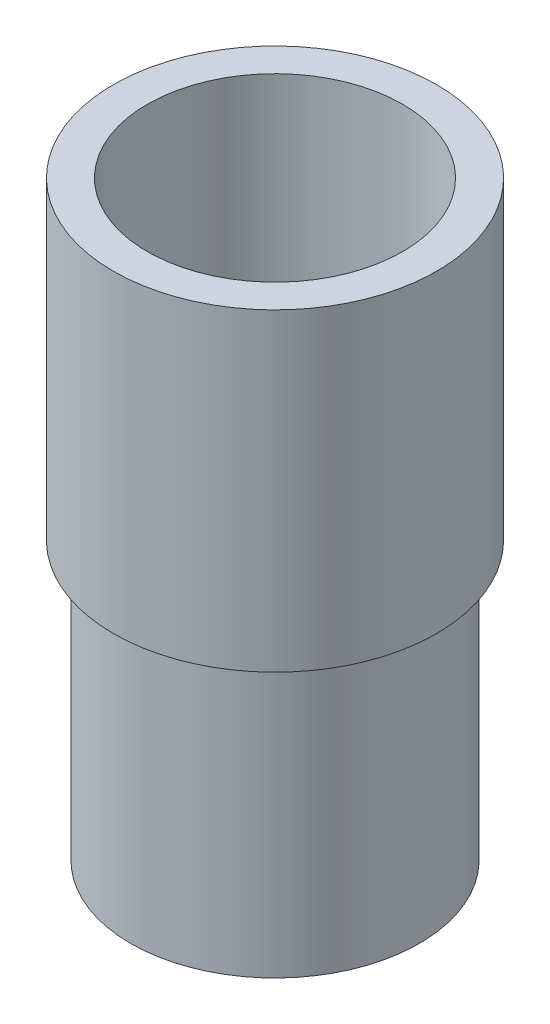
SolidWorks part; units mm, degrees
ref_plane "Front Plane" through (0, 0, 0) normal (0, 0, 1) x (1, 0, 0)
ref_plane "Top Plane" through (0, 0, 0) normal (0, 1, 0) x (1, 0, 0)
ref_plane "Right Plane" through (0, 0, 0) normal (1, 0, 0) x (0, 0, -1)
sketch "Sketch1" plane through (0, 0, 0) normal (0, 0, 1) x (1, 0, 0)
  line L0 (0, 0) -> (0, 65) construction
  line L2 (14.0462, 0) -> (15.875, 0)
  line L3 (14.0462, 0) -> (14.0462, 30.48)
  line L4 (14.0462, 30.48) -> (15.875, 30.48)
  line L5 (15.875, 0) -> (15.875, 30.48)
  line L6 (14.0462, 30.48) -> (17.78, 30.48)
  line L7 (14.0462, 30.48) -> (14.0462, 65)
  line L8 (14.0462, 65) -> (17.78, 65)
  line L9 (17.78, 30.48) -> (17.78, 65)
  line L10 (14.0462, 40.48) -> (0, 40.48)
  line L11 (14.0462, 40.48) -> (14.0462, 30.48)
  line L12 (14.0462, 30.48) -> (0, 30.48)
  line L13 (0, 40.48) -> (0, 30.48)
  point P14 (14.0462, 30.0423)
  dimension "D1" = 65
  dimension "D2" = 31.75
  dimension "D3" = 1.8288
  dimension "D4" = 30.48
  dimension "D5" = 35.56
  dimension "D6" = 10
revolve "Revolve1" add sketch "Sketch1" angle 360 about L0 region at (14.9606, 15.24, 0) region at (15.9131, 47.74, 0) region at (7.0231, 35.48, 0)
